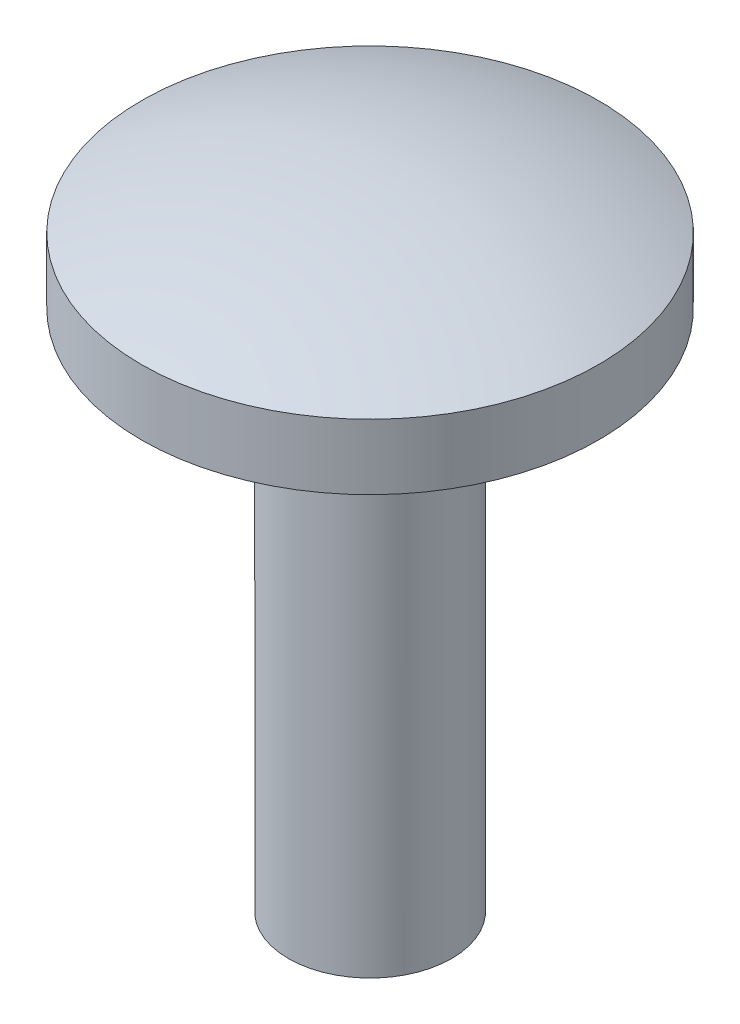
SolidWorks part; units mm, degrees
material "SS BS EN 10088-2 1.4301"
ref_plane "Front" through (0, 0, 0) normal (0, 0, 1) x (1, 0, 0)
ref_plane "Top" through (0, 0, 0) normal (0, 1, 0) x (1, 0, 0)
ref_plane "Right" through (0, 0, 0) normal (1, 0, 0) x (0, 0, -1)
sketch "Sketch1" plane through (0, 0, 0) normal (0, 1, 0) x (1, 0, 0)
  circle A0 centre (0, 0) radius 3.5
  dimension "D1" = 7
extrude "Boss-Extrude1" add sketch "Sketch1" along normal blind 1
dome "Dome1" faces to dome 1 distance 0.75 reverse direction no elliptical dome no face at (0, 1, 3.5) parameters "D1"=0.75
sketch "Sketch2" plane through (0, 0, 0) normal (0, -1, 0) x (1, 0, 0)
  circle A0 centre (0, 0) radius 1.25
  dimension "D1" = 2.5
extrude "Boss-Extrude2" add sketch "Sketch2" along normal blind 8
